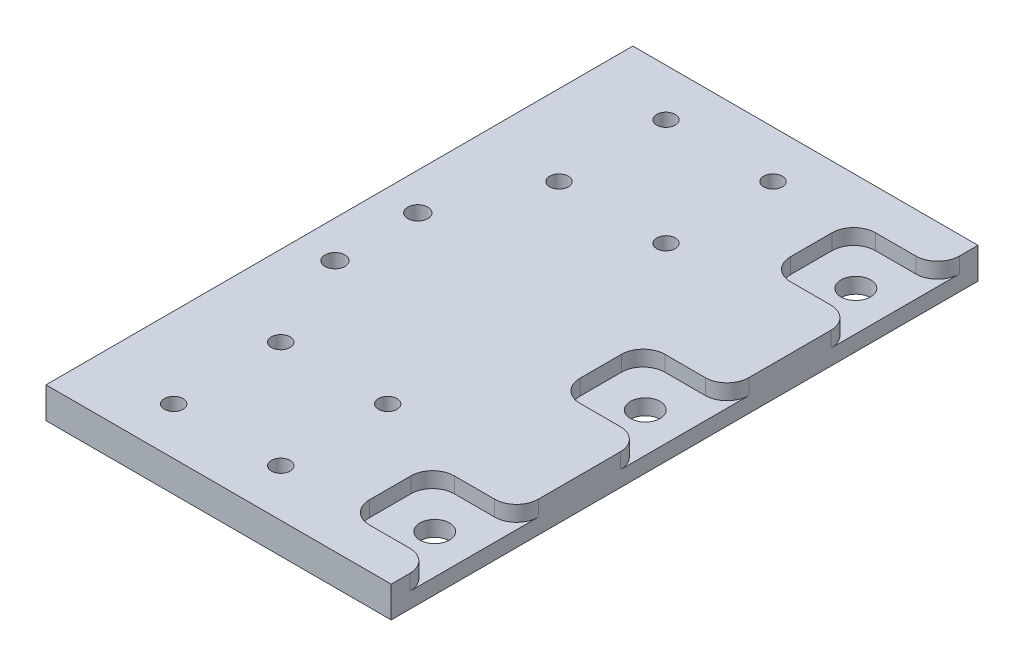
SolidWorks part; units mm, degrees
material "Onyx w/ CF"
ref_plane "Front Plane" through (0, 0, 0) normal (0, 0, 1) x (1, 0, 0)
ref_plane "Top Plane" through (0, 0, 0) normal (0, 1, 0) x (1, 0, 0)
ref_plane "Right Plane" through (0, 0, 0) normal (1, 0, 0) x (0, 0, -1)
sketch "Sketch1" plane through (0, 0, 0) normal (0, 1, 0) x (1, 0, 0)
  line L1 (-25, 47.5) -> (25, 47.5)
  line L2 (-25, 47.5) -> (-25, -47.5)
  line L3 (-25, -47.5) -> (25, -47.5)
  line L4 (25, 47.5) -> (25, -47.5)
  line L5 (-25, 47.5) -> (25, -47.5) construction
  line L6 (-25, -47.5) -> (25, 47.5) construction
  point P0 (0, 0)
  dimension "D1" = 50
  dimension "D2" = 95
extrude "Boss-Extrude1" add sketch "Sketch1" along normal mid plane 4.5
hole_wizard "M2.5 Clearance Hole1" positions "Sketch2" profile "Sketch3" hole size "M2.5" standard "ANSI Metric"
sketch "Sketch2" plane through (0, 2.25, 0) normal (0, 1, 0) x (1, 0, 0)
  line L1 (2.15, -20.15) -> (-13.35, -20.15)
  line L2 (2.15, -20.15) -> (2.15, -35.65)
  line L3 (2.15, -35.65) -> (-13.35, -35.65)
  line L4 (-13.35, -20.15) -> (-13.35, -35.65)
  line L5 (2.15, -20.15) -> (-13.35, -35.65) construction
  line L6 (2.15, -35.65) -> (-13.35, -20.15) construction
  line L9 (-25, -47.5) -> (25, -47.5) construction
  line L10 (-25, 47.5) -> (-25, -47.5) construction
  point P0 (2.15, -20.15)
  point P2 (2.15, -35.65)
  point P5 (-13.35, -35.65)
  point P8 (-13.35, -20.15)
  point P51 (-5.6, -27.9)
  dimension "D1" = 15.5
  dimension "D2" = 19.6
  dimension "D3" = 19.4
sketch "Sketch3" plane through (2.15, 2.25, 20.15) normal (1, 0, 0) x (0, 0, 1)
  line L0 (0, 0) -> (0, 7.1612)
  line L1 (0, 7.1612) -> (1.35, 6.35)
  line L2 (1.35, 6.35) -> (1.35, 0)
  line L5 (1.35, 0) -> (0, 0)
  line L10 (0, 7.1612) -> (-1.35, 6.35) construction
  line L11 (0, -6.35) -> (0, 107.95) construction
  dimension "Hole Dia." = 2.7
  dimension "Hole Depth" = 6.35
  dimension "Drill Angle" = 118
sketch "Sketch4" plane through (0, 2.25, 0) normal (0, 1, 0) x (1, 0, 0)
  line L0 (-25, -47.5) -> (25, -47.5) construction
  line L1 (-25, -47.5) -> (25, -47.5)
  line L2 (-25, -47.5) -> (-25, -42.5)
  line L3 (25, -47.5) -> (25, -42.5)
  line L4 (25, -42.5) -> (-25, -42.5)
  dimension "D1" = 5
extrude "Cut-Extrude1" cut sketch "Sketch4" against normal through all
mirror "Mirror1" about plane through (0, 0, 0) normal (0, 0, 1) of "Cut-Extrude1", "M2.5 Clearance Hole1"
sketch "Sketch5" plane through (0, 2.25, 0) normal (0, 1, 0) x (1, 0, 0)
  line L0 (25, -42.5) -> (25, 42.5) construction
  line L1 (25, -36.5) -> (16, -36.5) construction
  line L3 (25, -24.5) -> (16, -24.5) construction
  line L4 (13, -33.5) -> (13, -27.5) construction
  line L5 (22, -36.5) -> (16, -36.5) construction
  line L7 (25, -36.6524) -> (16, -36.6524)
  line L8 (12.8476, -33.5) -> (12.8476, -27.5)
  line L9 (25, -24.3476) -> (16, -24.3476)
  line L10 (25, 6.1524) -> (25, -6.1524)
  line L11 (25, -6.1524) -> (16, -6.1524)
  line L12 (12.8476, -3) -> (12.8476, 3)
  line L13 (25, 6.1524) -> (16, 6.1524)
  line L14 (25, 36.6524) -> (25, 24.3476)
  line L15 (25, 24.3476) -> (16, 24.3476)
  line L16 (12.8476, 27.5) -> (12.8476, 33.5)
  line L17 (25, 36.6524) -> (16, 36.6524)
  line L19 (22, -36.6524) -> (16, -36.6524) construction
  line L20 (25, -36.6524) -> (25, -24.3476)
  line L21 (25, -42.5) -> (-25, -42.5) construction
  arc A0 (16, -24.5) -> (13, -27.5) centre (16, -27.5) ccw construction
  arc A1 (16, -36.5) -> (13, -33.5) centre (16, -33.5) cw construction
  arc A4 (16, -36.6524) -> (12.8476, -33.5) centre (16, -33.5) cw
  arc A5 (16, -24.3476) -> (12.8476, -27.5) centre (16, -27.5) ccw
  arc A9 (16, -6.1524) -> (12.8476, -3) centre (16, -3) cw
  arc A10 (16, 6.1524) -> (12.8476, 3) centre (16, 3) ccw
  arc A13 (16, 24.3476) -> (12.8476, 27.5) centre (16, 27.5) cw
  arc A14 (16, 36.6524) -> (12.8476, 33.5) centre (16, 33.5) ccw
  point P11 (13, -24.5)
  point P14 (13, -36.5)
  point P27 (12.8476, -30.5)
  point P28 (12.8476, 0)
  dimension "D3" = 3
  dimension "D1" = 12
  dimension "D4" = 12
  dimension "D6" = 3
  dimension "D2" = 12
  dimension "D5" = 0.1524
  dimension "D7" = 30.5
extrude "Cut-Extrude2" cut sketch "Sketch5" against normal blind 2.25
hole_wizard "M4 Clearance Hole1" positions "Sketch6" profile "Sketch7" hole size "M4" standard "ANSI Metric"
sketch "Sketch6" plane through (0, 0, 0) normal (0, 1, 0) x (1, 0, 0)
  line L0 (12.8476, -27.5) -> (12.8476, -33.5) construction
  line L2 (12.8476, 3) -> (12.8476, -3) construction
  line L5 (12.8476, 33.5) -> (12.8476, 27.5) construction
  line L6 (12.8476, 0) -> (25, 0) construction
  line L7 (12.8476, 3) -> (12.8476, -3) construction
  line L8 (25, -6.1524) -> (25, 6.1524) construction
  point P0 (19.3048, -30.5)
  point P2 (19.3048, 0)
  point P4 (19.3048, 30.5)
  point P13 (12.8476, -30.5)
  point P21 (12.8476, 0)
  point P30 (12.8476, 30.5)
  dimension "D1" = 5.6952
sketch "Sketch7" plane through (19.3048, 0, 30.5) normal (1, 0, 0) x (0, 0, 1)
  line L0 (0, 0) -> (0, 11.3919)
  line L1 (0, 11.3919) -> (2.15, 10.1)
  line L2 (2.15, 10.1) -> (2.15, 0)
  line L5 (2.15, 0) -> (0, 0)
  line L10 (0, 11.3919) -> (-2.15, 10.1) construction
  line L11 (0, -6.35) -> (0, 107.95) construction
  dimension "Hole Dia." = 4.3
  dimension "Hole Depth" = 10.1
  dimension "Drill Angle" = 118
fillet "Fillet1" radius 3.1524 6 edges at (25, 1.125, -36.6524) (25, 1.125, -24.3476) (25, 1.125, -6.1524) (25, 1.125, 6.1524) (25, 1.125, 24.3476) (25, 1.125, 36.6524)
hole_wizard "M2.5 Clearance Hole2" positions "Sketch8" profile "Sketch9" hole size "M2.5" standard "ANSI Metric" end condition through all
sketch "Sketch8" plane through (0, -2.25, 0) normal (0, -1, 0) x (-1, 0, 0)
  line L0 (19.642, 6) -> (19.642, -6)
  line L2 (25, 42.5) -> (25, -42.5) construction
  point P0 (19.642, 6)
  point P2 (19.642, -6)
  point P10 (19.642, 0)
  dimension "D1" = 12
  dimension "D2" = 5.358
sketch "Sketch9" plane through (-19.642, -2.25, -6) normal (1, 0, 0) x (0, 0, -1)
  line L0 (0, 0) -> (0, 4.5)
  line L1 (0, 4.5) -> (1.45, 4.5)
  line L2 (1.45, 4.5) -> (1.45, 0)
  line L5 (1.45, 0) -> (0, 0)
  line L11 (0, -6.35) -> (0, 107.95) construction
  dimension "Thru Hole Dia." = 2.9
  dimension "Thru Hole Depth" = 4.5
